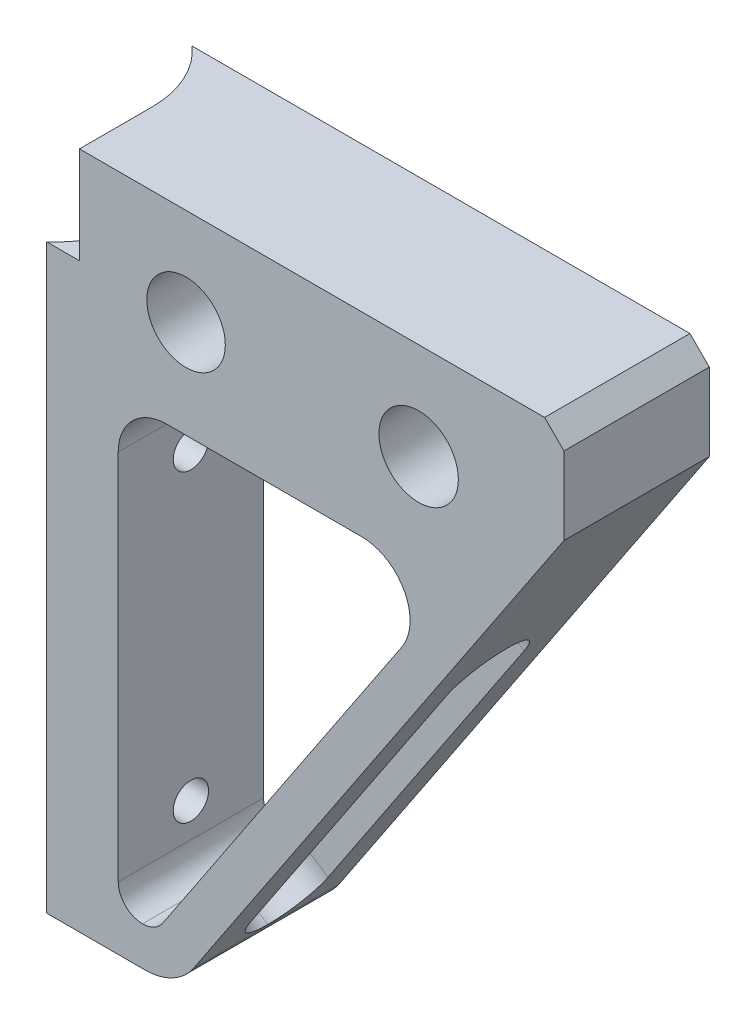
SolidWorks part; units mm, degrees
material "PET"
ref_plane "Přední rovina" through (0, 0, 0) normal (0, 0, 1) x (1, 0, 0)
ref_plane "Horní rovina" through (0, 0, 0) normal (0, 1, 0) x (1, 0, 0)
ref_plane "Pravá rovina" through (0, 0, 0) normal (1, 0, 0) x (0, 0, -1)
sketch "Skica1" plane through (0, 0, 0) normal (0, 0, 1) x (1, 0, 0)
  line L0 (0, 0) -> (10, 0)
  line L1 (10, 0) -> (50, 60)
  line L2 (50, 60) -> (50, 70)
  line L3 (50, 70) -> (0, 70)
  line L4 (0, 70) -> (0, 0)
  dimension "D1" = 50
  dimension "D2" = 10
  dimension "D3" = 10
  dimension "D4" = 70
extrude "Přidat vysunutím1" add sketch "Skica1" along normal blind 15
sketch "Skica2" plane through (0, 0, 15) normal (0, 0, 1) x (1, 0, 0)
  line L0 (0, 60) -> (52.1866, 60) construction
  line L1 (0, 70) -> (0, 0) construction
  line L2 (50, 70) -> (0, 70) construction
  line L3 (50, 60) -> (50, 70) construction
  circle A0 centre (35, 60) radius 4.1
  circle A1 centre (11, 60) radius 4 construction
  dimension "D2" = 8.2
  dimension "D4" = 8
  dimension "D1" = 10
  dimension "D3" = 15
  dimension "D5" = 24
extrude "Odebrat vysunutím1" cut sketch "Skica2" against normal through all
sketch "Skica3" plane through (0, 0, 15) normal (0, 0, 1) x (1, 0, 0)
  line L0 (35, 60) -> (11, 60) construction
  circle A0 centre (11, 60) radius 4.05
  dimension "D2" = 8.1
  dimension "D1" = 24
extrude "Odebrat vysunutím2" cut sketch "Skica3" against normal blind 10
sketch "Skica4" plane through (0, 0, 15) normal (0, 0, 1) x (1, 0, 0)
  line L10 (9, 49.9) -> (29.1167, 49.9)
  line L15 (4, 66) -> (4, 4)
  line L16 (4, 4) -> (7.8593, 4)
  line L17 (7.8593, 4) -> (46, 61.2111)
  line L18 (46, 61.2111) -> (46, 66)
  line L19 (46, 66) -> (4, 66)
  line L20 (4, 44.9) -> (4, 6.5)
  line L21 (6.5, 4) -> (6.5213, 4)
  line L22 (8.6014, 5.1132) -> (33.2769, 42.1265)
  circle A1 centre (35, 60) radius 4.1 construction
  arc A2 (6.5213, 4) -> (8.6014, 5.1132) centre (6.5213, 6.5) ccw
  arc A3 (4, 6.5) -> (6.5, 4) centre (6.5, 6.5) ccw
  arc A4 (33.2769, 42.1265) -> (29.1167, 49.9) centre (29.1167, 44.9) ccw
  arc A5 (4, 44.9) -> (9, 49.9) centre (9, 44.9) cw
  dimension "D3" = 2.5
  dimension "D4" = 5
  dimension "D2" = 6
  dimension "D1" = 4
extrude "Odebrat vysunutím3" cut sketch "Skica4" against normal through all
sketch "Skica5" plane through (0, 70, 0) normal (0, 1, 0) x (1, 0, 0)
  line L0 (50, -7.5) -> (-10, -7.5) construction
  line L1 (50, -15) -> (50, 0) construction
  line L2 (0, -15) -> (0, 0) construction
  line L3 (-3.3856, 0) -> (3, 0)
  line L4 (50, 0) -> (0, 0) construction
  line L5 (3, 0) -> (3, -15)
  line L6 (50, -15) -> (0, -15) construction
  line L7 (3, -15) -> (-3.3856, -15)
  arc A0 (-3.3856, -15) -> (-3.3856, 0) centre (-10, -7.5) ccw
  dimension "D1" = 20
  dimension "D2" = 3
extrude "Přidat vysunutím2" add sketch "Skica5" against normal up to surface (70 mm away) up to face at (5, 0, 7.5)
sketch "Skica6" plane through (0, 70, 0) normal (0, 1, 0) x (1, 0, 0)
  line L1 (-3.3856, -15) -> (0, -15)
  line L2 (-3.3856, -15) -> (-3.3856, -7.5)
  line L3 (-3.3856, -7.5) -> (0, -7.5)
  line L4 (0, -15) -> (0, -7.5)
  line L5 (-3.3856, -15) -> (0, -7.5) construction
  line L6 (-3.3856, -7.5) -> (0, -15) construction
  arc A0 (-3.3856, -15) -> (-3.3856, 0) centre (-10, -7.5) ccw construction
  point P4 (-1.6928, -11.25)
extrude "Odebrat vysunutím4" cut sketch "Skica6" against normal blind 10
sketch "Skica8" plane through (3.5949, -2.3966, 0) normal (-0.8321, 0.5547, 0) x (0, 0, 1)
  line L0 (7.5, 88.4632) -> (7.5, -0.9383) construction
  line L1 (0, 9.0257) -> (0, 53.5101) construction
  line L2 (15, 9.0257) -> (15, 53.5101) construction
  line L3 (0, 53.5101) -> (15, 53.5101) construction
  line L4 (3.5, 53.5101) -> (11.5, 53.5101)
  line L5 (3.5, 53.5101) -> (3.5, 9.0257)
  line L6 (3.5, 9.0257) -> (11.5, 9.0257)
  line L7 (11.5, 53.5101) -> (11.5, 9.0257)
  line L8 (3.5, 53.5101) -> (11.5, 9.0257) construction
  line L9 (3.5, 9.0257) -> (11.5, 53.5101) construction
  line L10 (0, 9.0257) -> (15, 9.0257) construction
  point P10 (7.5, 31.2679)
  dimension "D1" = 3.5
extrude "Odebrat vysunutím5" cut sketch "Skica8" against normal through all
fillet "Zaoblit1" radius 4 4 edges at (34.941, 41.0171, 3.5) (34.941, 41.0171, 11.5) (10.2655, 4.0038, 11.5) (10.2655, 4.0038, 3.5)
sketch "Skica9" plane through (4, 0, 0) normal (1, 0, 0) x (0, 0, -1)
  line L0 (-7.5, 0) -> (-7.5, 70) construction
  line L1 (-15, 0) -> (0, 0) construction
  line L2 (0, 44.9) -> (-15, 44.9) construction
  circle A0 centre (-7.5, 10) radius 1.825
  circle A1 centre (-7.5, 41.4) radius 1.825
  dimension "D1" = 3.65
  dimension "D2" = 3.65
  dimension "D3" = 10
  dimension "D4" = 3.5
extrude "Odebrat vysunutím6" cut sketch "Skica9" against normal through all
fillet "Zaoblit3" radius 6 1 edges at (10, 0, 7.5)
chamfer "Zkosení1" distance 2 angle 45 1 edges at (50, 70, 7.5)
